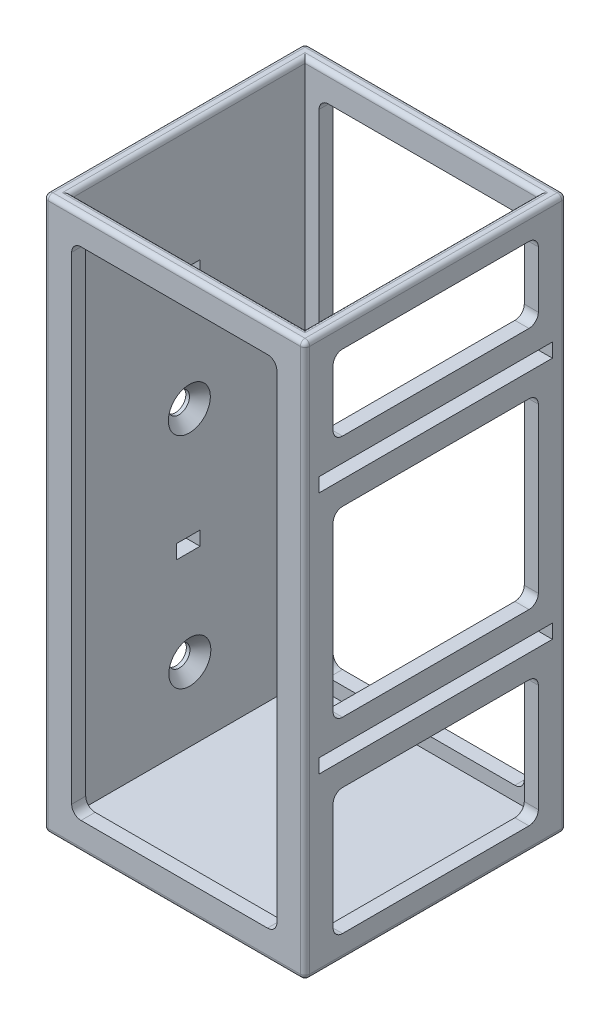
SolidWorks part; units mm, degrees
ref_plane "Front Plane" through (0, 0, 0) normal (0, 0, 1) x (1, 0, 0)
ref_plane "Top Plane" through (0, 0, 0) normal (0, 1, 0) x (1, 0, 0)
ref_plane "Right Plane" through (0, 0, 0) normal (1, 0, 0) x (0, 0, -1)
sketch "Sketch1" plane through (0, 0, 0) normal (0, 1, 0) x (1, 0, 0)
  line L0 (-27.894, 27.894) -> (27.894, 27.894)
  line L1 (-24.894, -24.894) -> (24.894, -24.894)
  line L2 (-24.894, -24.894) -> (-24.894, 24.894)
  line L3 (-24.894, 24.894) -> (24.894, 24.894)
  line L4 (24.894, -24.894) -> (24.894, 24.894)
  line L5 (-24.894, -24.894) -> (24.894, 24.894) construction
  line L6 (-24.894, 24.894) -> (24.894, -24.894) construction
  line L7 (27.894, -27.894) -> (27.894, 27.894)
  line L8 (-27.894, -27.894) -> (27.894, -27.894)
  line L9 (-27.894, -27.894) -> (-27.894, 27.894)
  point P0 (0, 0)
  dimension "D1" = 49.788
  dimension "D2" = 3
extrude "Boss-Extrude1" add sketch "Sketch1" along normal blind 3 contours L3 L4 L1 L2
extrude "Boss-Extrude2" add sketch "Sketch1<3>" along normal blind 118
sketch "Sketch1<3>" plane through (0, 0, 0) normal (0, 1, 0) x (1, 0, 0) same geometry as "Sketch1"
sketch "Sketch2" plane through (27.894, 0, 0) normal (1, 0, 0) x (0, 0, -1)
  line L0 (0, 118) -> (0, 91.923) construction
  line L1 (-27.894, 118) -> (27.894, 118) construction
  line L2 (-27.894, 118) -> (-27.894, 0) construction
  line L3 (-24.894, 91.923) -> (24.894, 91.923)
  line L4 (-24.894, 91.923) -> (-24.894, 88.923)
  line L5 (-24.894, 88.923) -> (24.894, 88.923)
  line L6 (24.894, 91.923) -> (24.894, 88.923)
  line L7 (27.894, 118) -> (27.894, 0) construction
  line L8 (0, 118) -> (0, 39.974) construction
  line L9 (-27.894, 0) -> (27.894, 0) construction
  line L10 (-24.894, 39.974) -> (24.894, 39.974)
  line L11 (-24.894, 39.974) -> (-24.894, 36.974)
  line L12 (-24.894, 36.974) -> (24.894, 36.974)
  line L13 (24.894, 39.974) -> (24.894, 36.974)
  line L14 (-21.894, 83.923) -> (21.894, 83.923)
  line L15 (-21.894, 83.923) -> (-21.894, 44.974)
  line L16 (-21.894, 44.974) -> (21.894, 44.974)
  line L17 (21.894, 83.923) -> (21.894, 44.974)
  line L18 (-21.894, 31.974) -> (21.894, 31.974)
  line L19 (-21.894, 31.974) -> (-21.894, 5)
  line L20 (-21.894, 5) -> (21.894, 5)
  line L21 (21.894, 31.974) -> (21.894, 5)
  line L23 (-21.894, 113) -> (21.894, 113)
  line L24 (-21.894, 113) -> (-21.894, 96.923)
  line L25 (-21.894, 96.923) -> (21.894, 96.923)
  line L26 (21.894, 113) -> (21.894, 96.923)
  point P11 (24.894, 90.423)
  dimension "D1" = 26.077
  dimension "D2" = 3
  dimension "D3" = 3
  dimension "D4" = 3
  dimension "D5" = 78.026
  dimension "D6" = 3
  dimension "D7" = 3
  dimension "D8" = 3
  dimension "D9" = 5
  dimension "D10" = 5
  dimension "D11" = 5
  dimension "D12" = 5
  dimension "D13" = 6
  dimension "D14" = 6
  dimension "D15" = 6
  dimension "D16" = 6
  dimension "D17" = 5
  dimension "D18" = 5
  dimension "D19" = 6
  dimension "D20" = 6
extrude "Cut-Extrude1" cut sketch "Sketch2" against normal blind 3
fillet "Fillet1" radius 2 12 edges at (26.394, 5, -21.894) (26.394, 31.974, -21.894) (26.394, 31.974, 21.894) (26.394, 5, 21.894) (26.394, 44.974, -21.894) (26.394, 83.923, -21.894) (26.394, 83.923, 21.894) (26.394, 44.974, 21.894) (26.394, 96.923, 21.894) (26.394, 113, 21.894) (26.394, 113, -21.894) (26.394, 96.923, -21.894)
sketch "Sketch3" plane through (0, 0, -27.894) normal (0, 0, -1) x (-1, 0, 0)
  line L8 (-21.894, 6) -> (21.894, 6)
  line L9 (21.894, 6) -> (21.894, 112)
  line L10 (21.894, 112) -> (-21.894, 112)
  line L11 (-21.894, 112) -> (-21.894, 6)
  line L12 (-21.894, 6) -> (21.894, 6)
  line L13 (21.894, 6) -> (21.894, 112)
  line L14 (21.894, 112) -> (-21.894, 112)
  line L15 (-21.894, 112) -> (-21.894, 6)
  dimension "D1" = 6
extrude "Cut-Extrude2" cut sketch "Sketch3" against normal blind 56
fillet "Fillet2" radius 2 8 edges at (21.894, 112, 26.394) (-21.894, 112, 26.394) (-21.894, 6, 26.394) (21.894, 6, 26.394) (21.894, 6, -26.394) (21.894, 112, -26.394) (-21.894, 112, -26.394) (-21.894, 6, -26.394)
sketch "Sketch4" plane through (-27.894, 0, 0) normal (-1, 0, 0) x (0, 0, 1)
  line L0 (0, 118) -> (0, 91.923) construction
  line L1 (-27.894, 118) -> (27.894, 118) construction
  line L2 (0, 118) -> (0, 41.974) construction
  line L3 (-2.5, 91.923) -> (2.5, 91.923)
  line L4 (-2.5, 91.923) -> (-2.5, 88.923)
  line L5 (-2.5, 88.923) -> (2.5, 88.923)
  line L6 (2.5, 91.923) -> (2.5, 88.923)
  line L7 (27.894, 118) -> (27.894, 0) construction
  line L8 (-2.5, 41.974) -> (2.5, 41.974)
  line L9 (-2.5, 41.974) -> (-2.5, 38.974)
  line L10 (-2.5, 38.974) -> (2.5, 38.974)
  line L11 (2.5, 41.974) -> (2.5, 38.974)
  line L12 (-21.894, 83.923) -> (21.894, 83.923) construction
  line L13 (-21.894, 83.923) -> (-21.894, 46.974) construction
  line L14 (-21.894, 46.974) -> (21.894, 46.974) construction
  line L15 (21.894, 83.923) -> (21.894, 46.974) construction
  line L16 (-27.894, 118) -> (-27.894, 0) construction
  line L17 (-21.894, 83.923) -> (21.894, 46.974) construction
  line L18 (-21.894, 46.974) -> (21.894, 83.923) construction
  line L19 (-27.894, 0) -> (27.894, 0) construction
  line L20 (-21.894, 33.974) -> (21.894, 33.974) construction
  line L21 (-21.894, 33.974) -> (-21.894, 5) construction
  line L22 (-21.894, 5) -> (21.894, 5) construction
  line L23 (21.894, 33.974) -> (21.894, 5) construction
  line L24 (-21.894, 33.974) -> (21.894, 5) construction
  line L25 (-21.894, 5) -> (21.894, 33.974) construction
  point P9 (0, 91.923)
  point P15 (0, 41.974)
  point P24 (0, 65.4485)
  point P31 (0, 19.487)
  dimension "D1" = 26.077
  dimension "D2" = 5
  dimension "D3" = 76.026
  dimension "D4" = 5
  dimension "D5" = 3
  dimension "D6" = 3
  dimension "D7" = 6
  dimension "D8" = 6
  dimension "D9" = 5
  dimension "D10" = 5
  dimension "D11" = 5
  dimension "D12" = 5
extrude "Cut-Extrude3" cut sketch "Sketch4" against normal blind 3
hole_wizard "CSK for M4 SFHCS1" positions "3DSketch1" profile "Sketch7" countersink size "M4" standard "ANSI Metric" end condition through all
sketch3d "3DSketch1"
  line L0 (27.894, 83.3372, 21.3082) -> (27.894, 47.7394, -21.7418) construction
  line L1 (27.894, 31.8218, 20.6594) -> (27.894, 5.5858, -21.3082) construction
  arc A0 (27.894, 81.923, 21.894) -> (27.894, 83.923, 19.894) centre (27.894, 81.923, 19.894) ccw construction
  arc A1 (27.894, 46.974, -21.894) -> (27.894, 44.974, -19.894) centre (27.894, 46.974, -19.894) ccw construction
  arc A2 (27.894, 29.974, 21.894) -> (27.894, 31.974, 19.894) centre (27.894, 29.974, 19.894) ccw construction
  arc A3 (27.894, 7, -21.894) -> (27.894, 5, -19.894) centre (27.894, 7, -19.894) ccw construction
  point P0 (-24.894, 65.5383, -0.2168)
  point P8 (25.894, 81.923, 19.894)
  point P12 (25.894, 46.974, -19.894)
  point P16 (27.894, 65.5383, -0.2168)
  point P20 (-24.894, 18.7038, -0.3244)
  point P28 (25.894, 29.974, 19.894)
  point P32 (25.894, 7, -19.894)
  point P37 (27.894, 18.7038, -0.3244)
sketch "Sketch7" plane through (-24.894, 65.5383, -0.2168) normal (0, 1, 0) x (0, 0, -1)
  line L0 (0, 0) -> (0, 3)
  line L1 (0, 3) -> (2.25, 3)
  line L2 (2.25, 3) -> (2.25, 2.23)
  line L3 (2.25, 2.23) -> (4.48, 0)
  line L5 (4.48, 0) -> (0, 0)
  line L6 (-2.25, 2.23) -> (-4.48, 0) construction
  line L11 (0, -6.35) -> (0, 107.95) construction
  dimension "Thru Hole Dia." = 4.5
  dimension "Thru Hole Depth" = 3
  dimension "Near C'Sink Dia." = 8.96
  dimension "Near C'Sink Angle" = 90
fillet "Fillet3" radius 1 16 edges at (0, 118, -27.894) (-27.894, 118, 0) (-24.894, 118, 0) (0, 118, -24.894) (0, 118, 27.894) (0, 118, 24.894) (24.894, 118, 0) (27.894, 118, 0) (0, 0, -27.894) (27.894, 0, 0) (0, 0, 27.894) (-27.894, 59, 27.894) (27.894, 59, 27.894) (-27.894, 59, -27.894) (27.894, 59, -27.894) (-27.894, 0, 0)
